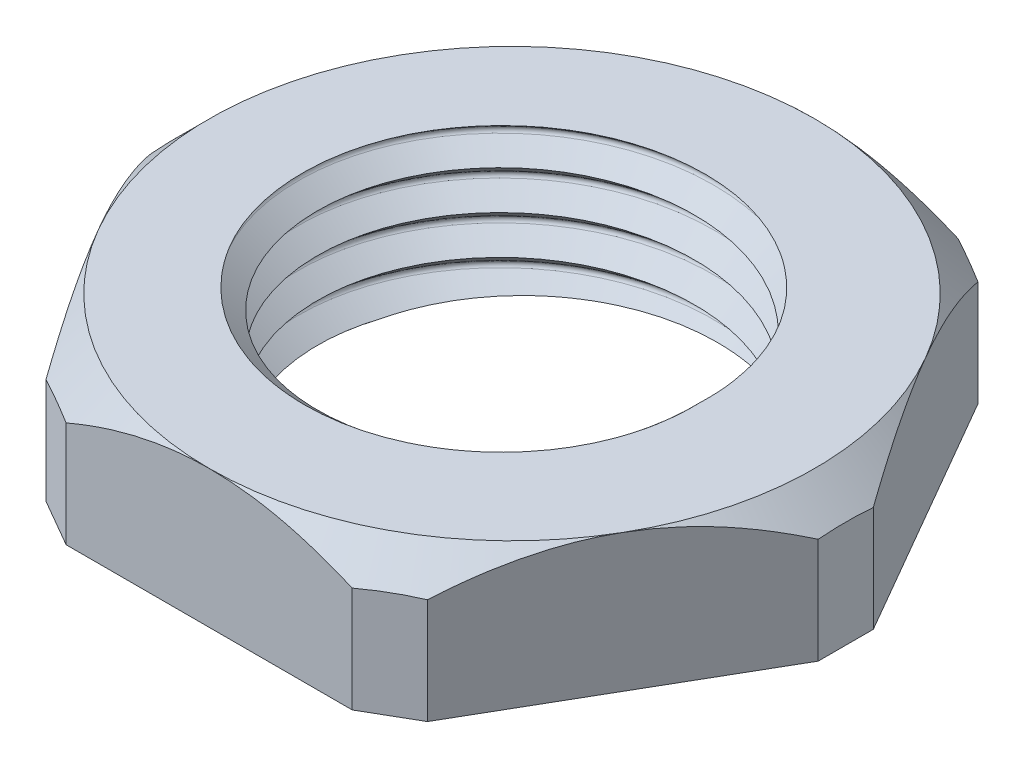
SolidWorks part; units mm, degrees
note: '?' marks a value the reader was unsure of.
material "PA Type 6"
ref_plane "Front Plane" through (0, 0, 0) normal (0, 0, 1) x (1, 0, 0)
ref_plane "Top Plane" through (0, 0, 0) normal (0, 1, 0) x (1, 0, 0)
ref_plane "Right Plane" through (0, 0, 0) normal (1, 0, 0) x (0, 0, -1)
ref_axis "Axis1" through (0, 3.0377, 0) along (0, -1, 0)?
sketch "ProfileS" plane through (0, 0, 0) normal (0, 1, 0) x (1, 0, 0)
  line L1 (6.3509, -11) -> (12.7017, 0)
  line L2 (12.7017, 0) -> (6.3509, 11)
  line L3 (6.3509, 11) -> (-6.3509, 11)
  line L4 (-6.3509, 11) -> (-12.7017, 0)
  line L5 (-12.7017, 0) -> (-6.3509, -11)
  line L6 (-6.3509, -11) -> (6.3509, -11)
  circle A2 centre (0, 0) radius 11 construction
  dimension "HexWidth" = 22
extrude "Profile" add sketch "ProfileS" along normal mid plane 5
sketch "ThreadOuterDiaRef" plane through (0, 2.5, 0) normal (0, 1, 0) x (1, 0, 0)
  circle A0 centre (0, 0) radius 7.6 construction
  dimension "MajorDia" = 15.2
sketch "LockNutThreadProfile" plane through (0, 0, 0) normal (0, 0, 1) x (1, 0, 0)
  line L0 (-6.8433, 3.2055) -> (-7.5462, 2.6157)
  line L2 (-7.5462, 2.3843) -> (-6.8433, 1.7945)
  line L3 (-6.8433, 1.7945) -> (-6.8433, 3.2055) construction
  line L4 (7.6, 2.5) -> (-7.6, 2.5) construction
  line L8 (-7.5462, 2.3843) -> (-7.6841, 2.5) construction
  line L9 (-7.6841, 2.5) -> (-7.5462, 2.6157) construction
  line L11 (-6.8433, 3.2055) -> (-6.7592, 3.2761)
  line L13 (-6.7592, 3.2761) -> (-6.7592, 1.7239)
  line L14 (-6.7592, 1.7239) -> (-6.8433, 1.7945)
  arc A0 (-7.5462, 2.6157) -> (-7.5462, 2.3843) centre (-7.4492, 2.5) ccw
  point P13 (-7.6, 2.5)
  dimension "PitchAngle" = 80
  dimension "HOffset" = 0.0841
  dimension "ThreadCutOffset" = 0.0841
sketch "MinorDiaRef" plane through (0, 2.5, 0) normal (0, 1, 0) x (-1, 0, 0)
  circle A0 centre (0, 0) radius 6.8433
  point P3 (6.8433, 0)
  dimension "Dim" = 13.6866
extrude "ThruHole" cut sketch "MinorDiaRef" against normal through all
sketch "Sketch7" plane through (0, 2.5, 0) normal (0, 1, 0) x (-1, 0, 0)
  circle A0 centre (0, 0) radius 6.8433
  circle A1 centre (0, 0) radius 6.8433 construction
curve "Helix/Spiral1" pitch 1.411 height 5 turns 3.5436 parameters "Pitch"=1.411
sweep "LockNutThread" cut profiles "LockNutThreadProfile" path "Helix/Spiral1" align with end faces yes
sketch "TopChamferS" plane through (0, 2.5, 0) normal (0, 1, 0) x (1, 0, 0)
  line L0 (6.3509, 11) -> (-6.3509, 11) construction
  circle A0 centre (0, 0) radius 11
extrude "TopChamfer" cut sketch "TopChamferS" against normal through all draft 45 flip side to cut
sketch "CornerFlatS" plane through (0, 0, 0) normal (0, 1, 0) x (1, 0, 0)
  line L0 (-5.1962, 11) -> (-6.9282, 10)
  line L1 (0, 11) -> (-6.3509, 11) construction
  line L2 (-6.3509, 11) -> (-9.5263, 5.5) construction
  line L3 (-6.3509, 11) -> (-6.0622, 10.5) construction
  dimension "CornerWidth" = 2
extrude "CornerFlat" cut sketch "CornerFlatS" against normal through all and the other way through all flip side to cut
pattern_circular "CirPattern1" count 6 over 360 of "CornerFlat"
sketch "EjectionPinHoleS" plane through (0, -2.5, 0) normal (0, -1, 0) x (-1, 0, 0)
  line L0 (3.8, -6.5818) -> (6.0622, -10.5) construction
  line L2 (5.1962, -11) -> (6.9282, -10) construction
  circle A0 centre (4.9311, -8.5409) radius 0.7
  circle A1 centre (0, 0) radius 7.6 construction
  dimension "Dia" = 1.4
extrude "EjectionPinHole" cut sketch "EjectionPinHoleS" against normal blind 1 draft 5
pattern_circular "CirPattern2" count 3 over 360 about axis through (0, 0, 0) along (0, 1, 0) of "EjectionPinHole"
equation "\"Radius@LockNutThreadProfile\"=.107*\"Pitch@LockNutThreadProfile\""
equation "\"HOffset@LockNutThreadProfile\" = .1 * \"Height@LockNutThreadProfile\""
equation "\"D3@Helix/Spiral1\"=\"Height@Profile\""
equation "\"ThreadCutOffset@LockNutThreadProfile\" = \"HOffset@LockNutThreadProfile\""
equation "\"Pitch@Helix/Spiral1\"=\"Pitch@LockNutThreadProfile\""
